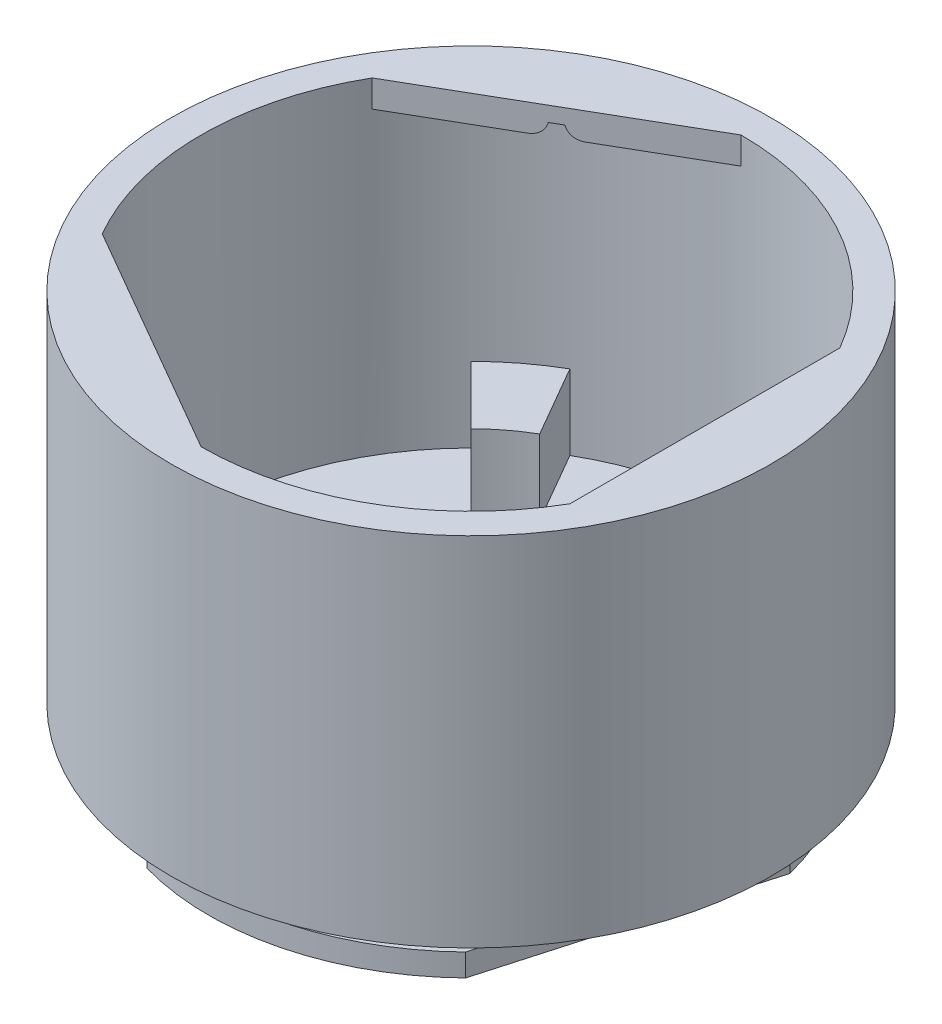
SolidWorks part; units mm, degrees
ref_plane "Front" through (0, 0, 0) normal (0, 0, 1) x (1, 0, 0)
ref_plane "Top" through (0, 0, 0) normal (0, 1, 0) x (1, 0, 0)
ref_plane "Right" through (0, 0, 0) normal (1, 0, 0) x (0, 0, -1)
sketch "Sketch1" plane through (0, 0, 0) normal (0, 1, 0) x (1, 0, 0)
  circle A0 centre (0, 0) radius 17.5
  circle A1 centre (0, 0) radius 12.5
extrude "Boss-Extrude1" add sketch "Sketch1" along normal blind 1.5
sketch "Sketch2" plane through (0, 1.5, 0) normal (0, 1, 0) x (1, 0, 0)
  line L0 (-10.1022, 10.4017) -> (-10.7989, 11.1191)
  line L1 (-14.0592, -3.5479) -> (-15.0289, -3.7926)
  line L2 (14.0592, 3.5479) -> (15.0289, 3.7926)
  line L3 (3.9571, 13.9496) -> (4.23, 14.9117)
  line L4 (-3.9571, -13.9496) -> (-4.23, -14.9117)
  line L5 (10.1022, -10.4017) -> (10.7989, -11.1191)
  line L6 (-12.1923, 12.5538) -> (4.7758, 16.8357)
  line L7 (16.9681, 4.2819) -> (12.1923, -12.5538)
  line L8 (-16.9681, -4.2819) -> (-4.7758, -16.8357)
  arc A0 (-16.9681, -4.2819) -> (-4.7758, -16.8357) centre (0, 0) ccw
  arc A1 (-10.7989, 11.1191) -> (-15.0289, -3.7926) centre (0, 0) ccw
  arc A2 (-10.1022, 10.4017) -> (-14.0592, -3.5479) centre (0, 0) ccw
  arc A3 (15.0289, 3.7926) -> (4.23, 14.9117) centre (0, 0) ccw
  arc A4 (14.0592, 3.5479) -> (3.9571, 13.9496) centre (0, 0) ccw
  arc A5 (-4.23, -14.9117) -> (10.7989, -11.1191) centre (0, 0) ccw
  arc A6 (-3.9571, -13.9496) -> (10.1022, -10.4017) centre (0, 0) ccw
  arc A7 (12.1923, -12.5538) -> (16.9681, 4.2819) centre (0, 0) ccw
  arc A8 (4.7758, 16.8357) -> (-12.1923, 12.5538) centre (0, 0) ccw
  point P13 (0, 0)
  dimension "D2" = 3
  dimension "D1" = 60
extrude "Cut-Extrude1" cut sketch "Sketch2" against normal blind 11
sketch "Sketch3" plane through (0, 1.5, 0) normal (0, 1, 0) x (1, 0, 0)
  circle A0 centre (0, 0) radius 12.5
  circle A1 centre (0, 0) radius 14.5
extrude "Boss-Extrude2" add sketch "Sketch3" along normal blind 2
sketch "Sketch4" plane through (0, 3.5, 0) normal (0, 1, 0) x (1, 0, 0)
  circle A0 centre (0, 0) radius 12.5
  circle A1 centre (0, 0) radius 20
extrude "Boss-Extrude3" add sketch "Sketch4" along normal blind 2
sketch "Sketch5" plane through (0, 5.5, 0) normal (0, 1, 0) x (1, 0, 0)
  circle A0 centre (0, 0) radius 20
  circle A1 centre (0, 0) radius 18
extrude "Boss-Extrude4" add sketch "Sketch5" along normal blind 20
sketch "Sketch6" plane through (0, 25.5, 0) normal (0, 1, 0) x (1, 0, 0)
  line L6 (-15.5885, 9) -> (0, 18)
  line L7 (15.5885, 9) -> (15.5885, -9)
  line L8 (-15.5885, -9) -> (0, -18)
  arc A0 (-15.5885, 9) -> (-15.5885, -9) centre (0, 0) ccw
  circle A1 centre (0, 0) radius 20
  arc A2 (15.5885, 9) -> (0, 18) centre (0, 0) ccw
  arc A3 (0, -18) -> (15.5885, -9) centre (0, 0) ccw
  point P18 (0, 0)
extrude "Boss-Extrude6" add sketch "Sketch6" along normal blind 1.8
sketch "Sketch7" plane through (0, 1.5, 0) normal (0, 1, 0) x (1, 0, 0)
  line L0 (0, 0) -> (3.5479, -14.0592) construction
  line L1 (3.3979, -15.123) -> (3.8363, -17.0743)
  line L2 (4.1847, -14.9244) -> (4.7246, -16.8502)
  arc A0 (-3.9571, -13.9496) -> (10.1022, -10.4017) centre (0, 0) ccw construction
  arc A1 (3.8363, -17.0743) -> (4.7246, -16.8502) centre (0, 0) ccw
  arc A3 (3.3979, -15.123) -> (4.1847, -14.9244) centre (0, 0) ccw
  dimension "D1" = 1.5
extrude "Boss-Extrude7" add sketch "Sketch7" along normal blind 0.8
fillet "Fillet3" radius 0.5 2 edges at (4.4547, 2.3, 15.8873) (3.6171, 2.3, 16.0987) first distance on face at (4.4547, 1.9, 15.8873) first distance on face at (3.6171, 1.9, 16.0987)
pattern_circular "CirPattern4" count 3 over 360 about axis through (0, 3.5, 0) along (0, 1, 0) of "Boss-Extrude7", "Fillet3"
ref_plane "Plane1" through (0, 25.3, 0) normal (0, 1, 0) x (1, 0, 0)
sketch "Sketch8" plane through (0, 25.3, 0) normal (0, 1, 0) x (1, 0, 0)
  line L0 (0, 0) -> (-7.7942, 13.5) construction
  line L1 (0, 18) -> (-15.5885, 9) construction
  line L2 (-8.0987, 13.2159) -> (-9.405, 15.3475)
  line L3 (-7.396, 13.6217) -> (-8.5889, 15.8187)
  arc A0 (-8.5889, 15.8187) -> (-9.405, 15.3475) centre (0, 0) ccw
  arc A1 (-7.396, 13.6217) -> (-8.0987, 13.2159) centre (0, 0) ccw
  dimension "D1" = 1.5
extrude "Cut-Extrude2" cut sketch "Sketch8" along normal blind 1
fillet "Fillet4" radius 1 2 edges at (-8.0148, 25.5, -14.7614) (-8.7764, 25.5, -14.3217) first distance on face at (-5.3886, 25.5, -16.0199) first distance on face at (-11.1793, 25.5, -12.6766)
pattern_circular "CirPattern5" count 3 over 360 about axis through (0, 27.3, 0) along (0, 1, 0) of "Cut-Extrude2", "Fillet4"
sketch "Sketch9" plane through (0, 5.5, 0) normal (0, 1, 0) x (1, 0, 0)
  line L0 (12.5, 0) -> (18, 0)
  line L1 (12.0741, 3.2352) -> (17.3867, 4.6587)
  arc A0 (12.5, 0) -> (12.0741, 3.2352) centre (0, 0) ccw
  arc A1 (18, 0) -> (17.3867, 4.6587) centre (0, 0) ccw
  dimension "D1" = 15
extrude "Boss-Extrude8" add sketch "Sketch9" along normal blind 5
pattern_circular "CirPattern6" count 3 over 360 about axis through (0, 5.5, 0) along (0, 1, 0) of "Boss-Extrude8"
